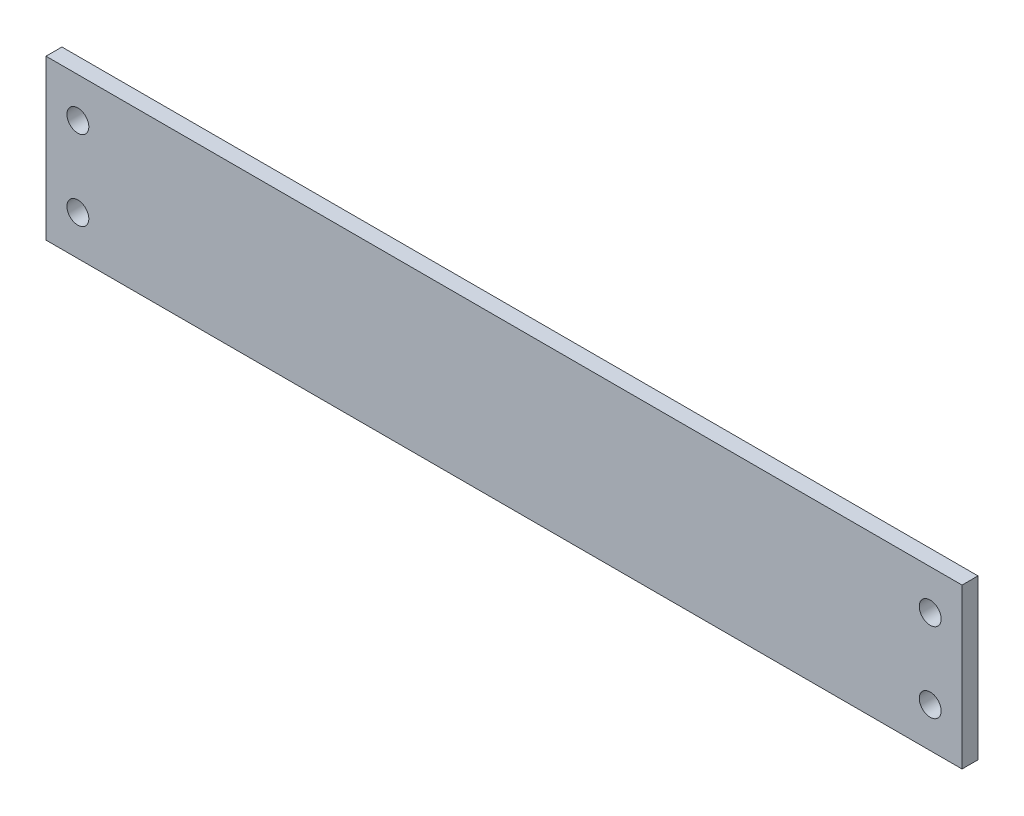
SolidWorks part; units mm, degrees
ref_plane "Front Plane" through (0, 0, 0) normal (0, 0, 1) x (1, 0, 0)
ref_plane "Top Plane" through (0, 0, 0) normal (0, 1, 0) x (1, 0, 0)
ref_plane "Right Plane" through (0, 0, 0) normal (1, 0, 0) x (0, 0, -1)
sketch "Extrusion Base Sketch" plane through (0, 0, 0) normal (0, 0, 1) x (1, 0, 0)
  line L0 (230, 40) -> (230, 0)
  line L1 (21.25, 3.25) -> (208.75, 3.25) construction
  line L2 (21.25, 3.25) -> (21.25, 36.75) construction
  line L3 (21.25, 36.75) -> (208.75, 36.75) construction
  line L4 (208.75, 3.25) -> (208.75, 36.75) construction
  line L5 (0, 40) -> (230, 40)
  line L6 (18, 40) -> (18, 0) construction
  line L7 (0, 0) -> (230, 0)
  line L8 (212, 40) -> (212, 0) construction
  line L9 (0, 40) -> (0, 0)
  line L10 (222, 30) -> (222, 10) construction
  line L11 (222, 20) -> (230, 20) construction
  line L12 (8, 30) -> (8, 10) construction
  line L13 (8, 20) -> (0, 20) construction
  dimension "D1" = 33.5
  dimension "D2" = 187.5
  dimension "D4" = 3.25
  dimension "D5" = 3.25
  dimension "D6" = 3.25
  dimension "D3" = 40
  dimension "D7" = 230
  dimension "D8" = 20
  dimension "D9" = 21.25
extrude "Extrusion Base Extrude" add sketch "Extrusion Base Sketch" against normal blind 4
hole_wizard "M5 Mounting Holes" positions "M5 Mounting Holes Position Sketch" profile "M5 Mounting Holes Profile Sketch" hole size "M5" standard "ANSI Metric" end condition through all
sketch "M5 Mounting Holes Position Sketch" plane through (0, 0, -4) normal (0, 0, -1) x (-1, 0, 0)
  point P0 (-222, 30)
  point P2 (-222, 10)
  point P4 (-8, 30)
  point P6 (-8, 10)
sketch "M5 Mounting Holes Profile Sketch" plane through (222, 30, -4) normal (1, 0, 0) x (0, 1, 0)
  line L0 (0, 0) -> (0, 4)
  line L1 (0, 4) -> (2.75, 4)
  line L2 (2.75, 4) -> (2.75, 0)
  line L5 (2.75, 0) -> (0, 0)
  line L11 (0, -6.35) -> (0, 107.95) construction
  dimension "Thru Hole Dia." = 5.5
  dimension "Thru Hole Depth" = 4
equation "\"Logo Height\"= 33.5mm"
equation "\"Total Height\"= 40mm"
equation "\"Border\"= ( \"Total Height\" - \"Logo Height\" ) / 2"
equation "\"Logo Length\"= 187.5mm"
equation "\"D1@Extrusion Base Sketch\" = \"Logo Height\""
equation "\"D2@Extrusion Base Sketch\" = \"Logo Length\""
equation "\"D4@Extrusion Base Sketch\" = \"Border\""
equation "\"D5@Extrusion Base Sketch\" = \"Border\""
equation "\"D6@Extrusion Base Sketch\" = \"Border\""
equation "\"D3@Extrusion Base Sketch\" = \"Total Height\""
